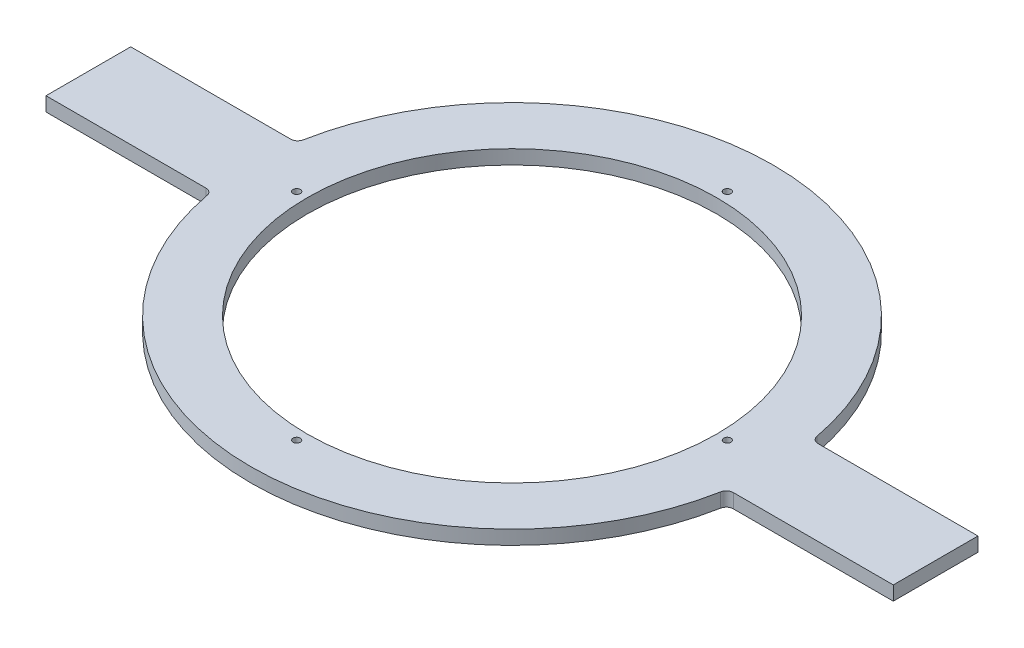
SolidWorks part; units mm, degrees
material "6061-T6 (SS)"
ref_plane "Front Plane" through (0, 0, 0) normal (0, 0, 1) x (1, 0, 0)
ref_plane "Top Plane" through (0, 0, 0) normal (0, 1, 0) x (1, 0, 0)
ref_plane "Right Plane" through (0, 0, 0) normal (1, 0, 0) x (0, 0, -1)
sketch "Sketch1" plane through (0, 0, 0) normal (0, 1, 0) x (1, 0, 0)
  line L0 (115.9201, 19.05) -> (190.5, 19.05)
  line L1 (-190.5, 19.05) -> (-115.9201, 19.05)
  line L2 (-190.5, 19.05) -> (-190.5, -19.05)
  line L3 (-190.5, -19.05) -> (-115.9201, -19.05)
  line L4 (190.5, 19.05) -> (190.5, -19.05)
  line L5 (-190.5, 19.05) -> (190.5, -19.05) construction
  line L6 (-190.5, -19.05) -> (190.5, 19.05) construction
  line L7 (115.9201, -19.05) -> (190.5, -19.05)
  circle A0 centre (0, 0) radius 92.075
  arc A1 (-115.9201, -19.05) -> (115.9201, -19.05) centre (0, 0) ccw
  arc A2 (115.9201, 19.05) -> (-115.9201, 19.05) centre (0, 0) ccw
  point P0 (0, 0)
  dimension "D3" = 184.15
  dimension "D4" = 25.4
  dimension "D1" = 381
  dimension "D2" = 38.1
extrude "Boss-Extrude1" add sketch "Sketch1" along normal blind 6.35
fillet "Fillet1" radius 3.175 4 edges at (-115.9201, 3.175, -19.05) (115.9201, 3.175, -19.05) (115.9201, 3.175, 19.05) (-115.9201, 3.175, 19.05)
hole_wizard "#4 Clearance Hole1" positions "Sketch2" profile "Sketch3" hole size "#4" standard "ANSI Inch" end condition through all
sketch "Sketch2" plane through (0, 6.35, 0) normal (0, 1, 0) x (1, 0, 0)
  circle A0 centre (0, 0) radius 96.8375
  circle A1 centre (0, 0) radius 92.075 construction
  point P7 (0, 96.8375)
  point P9 (96.8375, 0)
  point P11 (0, -96.8375)
  point P13 (-96.8375, 0)
  dimension "D1" = 4.7625
sketch "Sketch3" plane through (0, 6.35, -96.8375) normal (1, 0, 0) x (0, 0, 1)
  line L0 (0, 0) -> (0, 6.35)
  line L1 (0, 6.35) -> (1.6319, 6.35)
  line L2 (1.6319, 6.35) -> (1.6319, 0)
  line L5 (1.6319, 0) -> (0, 0)
  line L11 (0, -6.35) -> (0, 107.95) construction
  dimension "Thru Hole Dia." = 3.2639
  dimension "Thru Hole Depth" = 6.35
